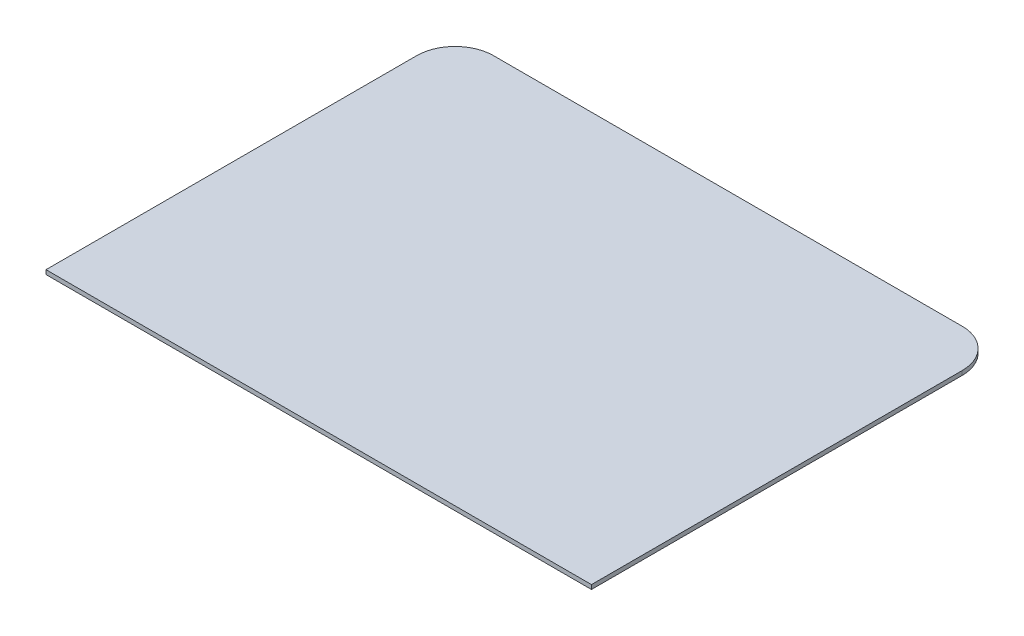
SolidWorks part; units mm, degrees
ref_plane "Front" through (0, 0, 0) normal (0, 0, 1) x (1, 0, 0)
ref_plane "Top" through (0, 0, 0) normal (0, 1, 0) x (1, 0, 0)
ref_plane "Right" through (0, 0, 0) normal (1, 0, 0) x (0, 0, -1)
sketch "Sketch1" plane through (0, 0, 0) normal (0, 1, 0) x (1, 0, 0)
  line L1 (203.2, -152.4) -> (-203.2, -152.4)
  line L2 (203.2, -152.4) -> (203.2, 152.4)
  line L3 (203.2, 152.4) -> (-203.2, 152.4)
  line L4 (-203.2, -152.4) -> (-203.2, 152.4)
  line L5 (203.2, -152.4) -> (-203.2, 152.4) construction
  line L6 (203.2, 152.4) -> (-203.2, -152.4) construction
  point P0 (0, 0)
  dimension "D1" = 406.4
  dimension "D2" = 304.8
extrude "Boss-Extrude1" add sketch "Sketch1" along normal blind 3.175
fillet "Fillet1" radius 28.575 2 edges at (-203.2, 1.5875, -152.4) (203.2, 1.5875, -152.4)
